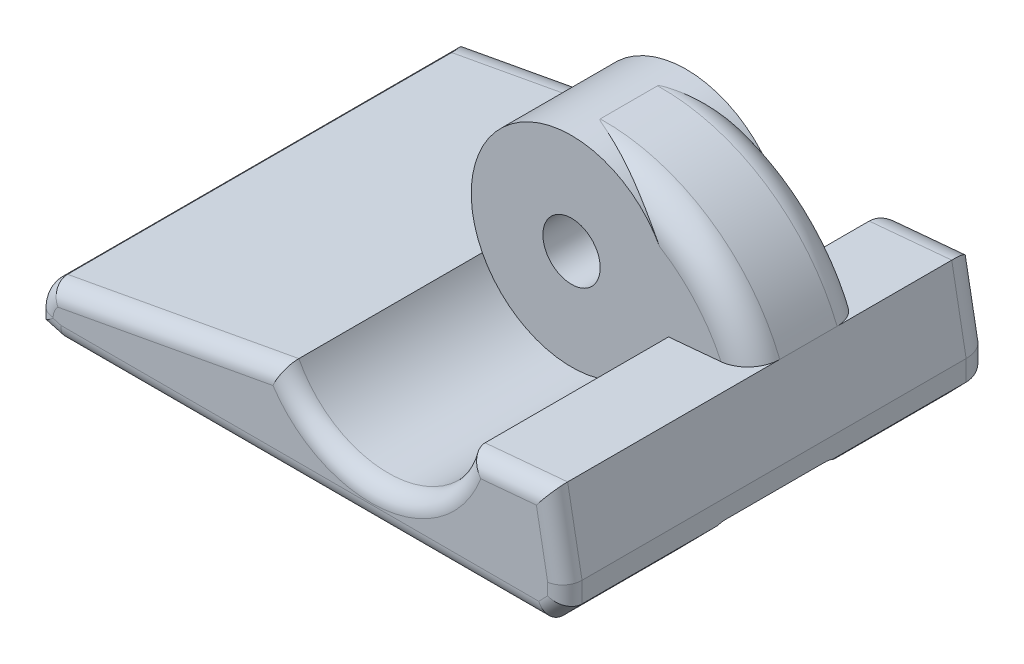
SolidWorks part; units mm, degrees
ref_plane "Front Plane" through (0, 0, 0) normal (0, 0, 1) x (1, 0, 0)
ref_plane "Top Plane" through (0, 0, 0) normal (0, 1, 0) x (1, 0, 0)
ref_plane "Right Plane" through (0, 0, 0) normal (1, 0, 0) x (0, 0, -1)
sketch "Sketch1" plane through (0, 0, 0) normal (0, 0, 1) x (1, 0, 0)
  line L0 (-31.135, -15.9878) -> (-111.836, -30.8747)
  line L1 (-116.8768, -40.2467) -> (-116.8768, -41.0471)
  line L2 (-116.8768, -41.0471) -> (-116.8768, -45.2391)
  line L3 (-108.8988, -47.4713) -> (61.1012, -47.4713)
  line L4 (67.6623, -40.7184) -> (67.6623, -33.5707)
  line L5 (67.6623, -33.5707) -> (62.6411, -6.3511)
  line L6 (62.6411, -6.3511) -> (33.8349, -8.9553)
  line L7 (-116.8768, -45.2391) -> (-108.8988, -47.4713)
  line L8 (67.6623, -40.7184) -> (61.1012, -47.4713)
  circle A0 centre (0, 0) radius 35
  arc A1 (-116.8768, -41.0471) -> (-111.836, -30.8747) centre (-104.9, -40.6469) cw
  arc A2 (0, 35) -> (62.6411, -6.3511) centre (1.4982, -30.8522) cw
  dimension "D1" = 70
  dimension "D2" = 170
extrude "Boss-Extrude1" add sketch "Sketch1" along normal blind 150 contours A1 L1 L2 L7 L3 L8 L4 L5 L6 A0 L0 region at (-15.9712, -33.6356, 0)
extrude "Boss-Extrude5" add sketch "Sketch1<6>" along normal blind 40 from offset 40 contours A2 A0 L6 | A0 region at (0, 0, 0) region at (41.2365, 8.978, 0)
sketch "Sketch1<6>" plane through (0, 0, 0) normal (0, 0, 1) x (1, 0, 0) same geometry as "Sketch1"
sketch "Sketch2" plane through (0, 0, 0) normal (1, 0, 0) x (0, 0, -1)
  line L0 (-150, -47.4713) -> (0, -47.4713) construction
  line L1 (-49.9043, -47.4713) -> (-103.3815, -47.4713)
  line L2 (-49.9043, -47.4713) -> (-49.9043, -40.2467)
  line L3 (-49.9043, -40.2467) -> (-103.3815, -40.2467)
  line L4 (-103.3815, -47.4713) -> (-103.3815, -40.2467)
  line L5 (-150, -40.2467) -> (0, -40.2467) construction
extrude "Cut-Extrude1" cut sketch "Sketch2" against normal through all and the other way through all
sketch "Sketch3" plane through (0, 0, 80) normal (0, 0, 1) x (1, 0, 0)
  circle A0 centre (0, 0) radius 10
extrude "Cut-Extrude2" cut sketch "Sketch3" against normal through all
fillet "Fillet1" radius 10 2 edges at (37.7866, 24.1197, 40) (37.7866, 24.1197, 80)
fillet "Fillet2" radius 10 9 edges at (-23.8988, -47.4713, 0) (64.3817, -44.0948, 0) (67.6623, -37.1445, 0) (65.1517, -19.9609, 0) (48.238, -7.6532, 0) (3.7665, -34.7967, 0) (-71.4855, -23.4312, 0) (-24.6073, -40.2467, 49.9043) (-24.6073, -40.2467, 103.3815)
fillet "Fillet3" radius 6 10 edges at (-71.4855, -23.4312, 150) (3.7665, -34.7967, 150) (48.238, -7.6532, 150) (65.1517, -19.9609, 150) (67.6623, -37.1445, 150) (64.3817, -44.0948, 150) (-23.8988, -47.4713, 150) (-112.8878, -46.3552, 150) (-116.8768, -42.7429, 150) (-115.4538, -34.9704, 150)
